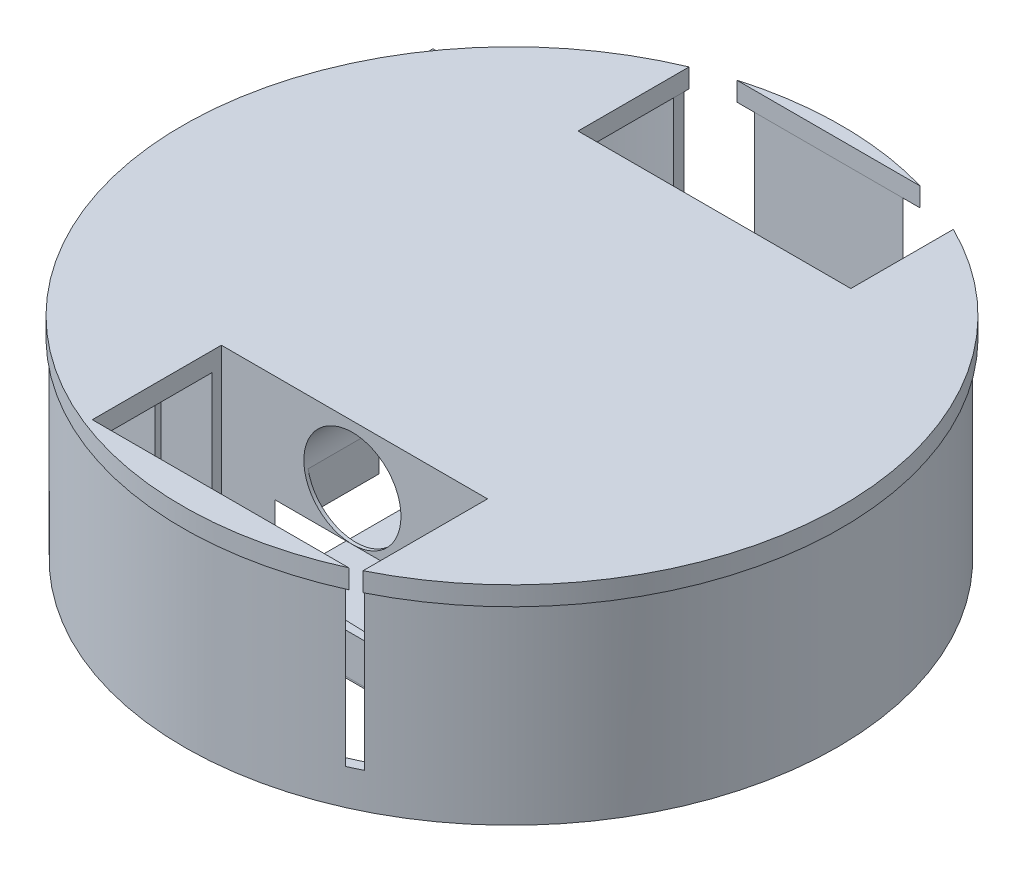
SolidWorks part; units mm, degrees
ref_plane "Front Plane" through (0, 0, 0) normal (0, 0, 1) x (1, 0, 0)
ref_plane "Top Plane" through (0, 0, 0) normal (0, 1, 0) x (1, 0, 0)
ref_plane "Right Plane" through (0, 0, 0) normal (1, 0, 0) x (0, 0, -1)
sketch "MotorHoldersSketch" plane through (0, 0, 0) normal (0, 0, 1) x (1, 0, 0)
  line L0 (0, 0) -> (170, 0) construction
  line L1 (0, 0) -> (0, 23.41) construction
  line L2 (170, 0) -> (170, 23.41) construction
  circle A1 centre (170, 0) radius 23.41
ref_axis "MotorCenterAxis1" through (0, 0, 0) along (0, 0, 1)
ref_axis "MotorCenterAxis2" through (170, 0, 0) along (0, 0, 1)
extrude "MotorHolders" add sketch "MotorHoldersSketch" along normal blind 80 and the other way blind 80
sketch "Sketch3" plane through (0, 0, 0) normal (0, 0, 1) x (1, 0, 0)
  line L1 (1.9406, 21.133) -> (168.3435, 21.133)
  line L2 (1.9406, 21.133) -> (1.9406, 18.3155)
  line L3 (1.9406, 18.3155) -> (168.3435, 18.3155)
  line L4 (168.3435, 21.133) -> (168.3435, 18.3155)
sketch "Sketch4" plane through (0, 0, 0) normal (0, 1, 0) x (1, 0, 0)
  line L1 (221.2811, -76.3794) -> (-41.4939, -76.3794)
  line L2 (221.2811, -76.3794) -> (221.2811, 76.7331)
  line L3 (221.2811, 76.7331) -> (-41.4939, 76.7331)
  line L4 (-41.4939, -76.3794) -> (-41.4939, 76.7331)
extrude "Cut-Extrude1" cut sketch "Sketch4" against normal blind 26
ref_axis "Axis3" through (170, 0, 0) along (0, -1, 0)
sketch3d "ReferencePlanePosition"
  line L0 (170, 0, 0) -> (170, -34.8293, 0)
  line L1 (170, 0, 0) -> (170, -38.994, 0) construction
ref_plane "ReferencePlane" through (170, -34.8293, 0) normal (0, -1, 0) x (-1, 0, 0)
sketch "Sketch6" plane through (170, -34.8293, 0) normal (0, -1, 0) x (-1, 0, 0)
  line L1 (118.9411, 77.3242) -> (78.3714, 77.3242)
  line L2 (118.9411, 77.3242) -> (118.9411, 63.9034)
  line L3 (118.9411, 63.9034) -> (78.3714, 63.9034)
  line L4 (78.3714, 77.3242) -> (78.3714, 63.9034)
  line L5 (102.8829, -41.5305) -> (78.545, -41.5305)
  line L6 (102.8829, -41.5305) -> (102.8829, -79.7918)
  line L7 (102.8829, -79.7918) -> (78.545, -79.7918)
  line L8 (78.545, -41.5305) -> (78.545, -79.7918)
  line L9 (75.6651, 77.8627) -> (19.9904, 77.8627)
  line L10 (75.6651, 77.8627) -> (75.6651, 40.7512)
  line L11 (75.6651, 40.7512) -> (19.9904, 40.7512)
  line L12 (19.9904, 77.8627) -> (19.9904, 40.7512)
  line L13 (76.5596, -44.1716) -> (20.0852, -44.1716)
  line L14 (76.5596, -44.1716) -> (76.5596, -79.4437)
  line L15 (76.5596, -79.4437) -> (20.0852, -79.4437)
  line L16 (20.0852, -44.1716) -> (20.0852, -79.4437)
  line L21 (41.3552, 69.1777) -> (28.5109, 69.1777)
  line L22 (41.3552, 69.1777) -> (41.3552, 50.8413)
  line L23 (41.3552, 50.8413) -> (28.5109, 50.8413)
  line L24 (28.5109, 69.1777) -> (28.5109, 50.8413)
  line L25 (43.3068, -72.8101) -> (32.1723, -72.8101)
  line L26 (43.3068, -72.8101) -> (43.3068, -54.7747)
  line L27 (43.3068, -54.7747) -> (32.1723, -54.7747)
  line L28 (32.1723, -72.8101) -> (32.1723, -54.7747)
  line L29 (101.8834, -71.9977) -> (88.494, -71.9977)
  line L30 (101.8834, -71.9977) -> (101.8834, -61.6501)
  line L31 (101.8834, -61.6501) -> (88.494, -61.6501)
  line L32 (88.494, -71.9977) -> (88.494, -61.6501)
  line L37 (66.2772, 51.3198) -> (53.8697, 51.3198)
  line L38 (66.2772, 51.3198) -> (66.2772, 67.7632)
  line L39 (66.2772, 67.7632) -> (53.8697, 67.7632)
  line L40 (53.8697, 51.3198) -> (53.8697, 67.7632)
  line L45 (68.2481, -69.8638) -> (51.7107, -69.8638)
  line L46 (68.2481, -69.8638) -> (68.2481, -55.4273)
  line L47 (68.2481, -55.4273) -> (51.7107, -55.4273)
  line L48 (51.7107, -69.8638) -> (51.7107, -55.4273)
  line L49 (-20.7001, -79.4437) -> (-48.8506, -79.4437)
  line L50 (-20.7001, -79.4437) -> (-20.7001, -54.5097)
  line L51 (-20.7001, -54.5097) -> (-48.8506, -54.5097)
  line L52 (-48.8506, -79.4437) -> (-48.8506, -54.5097)
  line L53 (-18.3873, 77.8627) -> (-49.0581, 77.8627)
  line L54 (-18.3873, 77.8627) -> (-18.3873, 51.5325)
  line L55 (-18.3873, 51.5325) -> (-49.0581, 51.5325)
  line L56 (-49.0581, 77.8627) -> (-49.0581, 51.5325)
  line L57 (-41.8141, -72.8101) -> (-31.6362, -72.8101)
  line L58 (-41.8141, -72.8101) -> (-41.8141, -62.9794)
  line L59 (-41.8141, -62.9794) -> (-31.6362, -62.9794)
  line L60 (-31.6362, -72.8101) -> (-31.6362, -62.9794)
  line L61 (-31.6362, 69.1777) -> (-41.5347, 69.1777)
  line L62 (-31.6362, 69.1777) -> (-31.6362, 58.5421)
  line L63 (-31.6362, 58.5421) -> (-41.5347, 58.5421)
  line L64 (-41.5347, 69.1777) -> (-41.5347, 58.5421)
extrude "PowerBankHolders" add sketch "Sketch6" along normal blind 30 and the other way blind 59 separate body
sketch3d "3DSketch3"
  line L0 (170, 0, 0) -> (170, -64.5, 0) construction
ref_plane "Plane2" through (170, -64.5, 0) normal (0, -1, 0) x (-1, 0, 0)
sketch "Sketch7" plane through (170, -64.5, 0) normal (0, -1, 0) x (-1, 0, 0)
  line L1 (-9.5047, -80.801) -> (181.32, -80.801)
  line L2 (-9.5047, -80.801) -> (-9.5047, 73.8662)
  line L3 (-9.5047, 73.8662) -> (181.32, 73.8662)
  line L4 (181.32, -80.801) -> (181.32, 73.8662)
  line L5 (151.8712, -54.3972) -> (26.5361, -54.3972)
  line L6 (151.8712, -54.3972) -> (151.8712, 46.2413)
  line L7 (151.8712, 46.2413) -> (26.5361, 46.2413)
  line L8 (26.5361, -54.3972) -> (26.5361, 46.2413)
ref_point "Point1"
sketch "MotorHolderExtrudeSketch" plane through (0, 0, 0) normal (0, 0, 1) x (1, 0, 0)
  circle A0 centre (170, 0) radius 20.415
  circle A4 centre (170, 0) radius 23.41 construction
ref_point "TopOfMotors"
ref_plane "TangentToTopOfMotors" through (0, -20.415, 0) normal (0, 1, 0) x (1, 0, 0)
ref_plane "BottomOfPowerBankRegion" through (0, -20.425, 0) normal (0, 1, 0) x (1, 0, 0)
ref_point "CenterAtBottomOfPowerBank"
ref_plane "TopOfPowerBankPlane" through (0, -54.425, 0) normal (0, 1, 0) x (1, 0, 0)
sketch "Sketch13" plane through (0, -54.425, 0) normal (0, 1, 0) x (1, 0, 0)
  line L1 (-19.4498, 72.5454) -> (166.1636, 72.5454)
  line L2 (-19.4498, 72.5454) -> (-19.4498, -78.2051)
  line L3 (-19.4498, -78.2051) -> (166.1636, -78.2051)
  line L4 (166.1636, 72.5454) -> (166.1636, -78.2051)
  line L5 (19.3173, -49.583) -> (137.9607, -49.583)
  line L6 (19.3173, -49.583) -> (19.3173, -21.0549)
  line L7 (19.3173, -21.0549) -> (137.9607, -21.0549)
  line L8 (137.9607, -49.583) -> (137.9607, -21.0549)
  line L9 (19.3173, 56.6778) -> (137.9607, 56.6778)
  line L10 (19.3173, 56.6778) -> (19.3173, 36.3234)
  line L11 (19.3173, 36.3234) -> (137.9607, 36.3234)
  line L12 (137.9607, 56.6778) -> (137.9607, 36.3234)
  line L13 (19.3173, 18.3186) -> (137.9607, 18.3186)
  line L14 (19.3173, 18.3186) -> (19.3173, -7.3615)
  line L15 (19.3173, -7.3615) -> (137.9607, -7.3615)
  line L16 (137.9607, 18.3186) -> (137.9607, -7.3615)
sketch "Sketch15" plane through (150.0096, 0, 0) normal (1, 0, 0) x (0, 0, -1)
  line L1 (72.5313, -25.7765) -> (45.7099, -25.7765)
  line L2 (72.5313, -25.7765) -> (72.5313, -24.2242)
  line L3 (72.5313, -24.2242) -> (45.7099, -24.2242)
  line L4 (45.7099, -25.7765) -> (45.7099, -24.2242)
ref_plane "Plane6" through (0, 0, 0) normal (0, 0, 1) x (1, 0, 0)
sketch "MotorGeometry1" plane through (0, 0, 0) normal (0, 0, 1) x (1, 0, 0)
  line L0 (170, 0) -> (170, -13.42)
  line L1 (170, 0) -> (170, -34.8293) construction
  line L2 (170, -13.42) -> (162.25, -13.42) construction
  line L3 (170, -13.42) -> (177.75, -13.42) construction
  line L4 (170, -13.42) -> (170, 7) construction
  line L5 (170, 0) -> (185.5, 0) construction
  line L6 (170, 0) -> (154.5, 0) construction
  line L7 (170, 0) -> (170, 13.42) construction
  line L8 (170, 0) -> (170, 23.41) construction
  line L9 (170, 13.42) -> (177.75, 13.42) construction
  line L10 (170, 13.42) -> (162.25, 13.42)
ref_axis "BoltAxisA" through (185.5, 0, 0) along (0, 0, 1)
ref_axis "BoltAxisB" through (177.75, -13.42, 0) along (0, 0, 1)
ref_axis "BoltAxisC" through (162.25, -13.42, 0) along (0, 0, 1)
ref_axis "BoltAxisD" through (154.5, 0, 0) along (0, 0, 1)
ref_axis "BoltAxisE" through (162.25, 13.42, 0) along (0, 0, 1)
ref_axis "BoltAxisF" through (177.75, 13.42, 0) along (0, 0, 1)
ref_point "Point6"
ref_point "Point7"
ref_point "Point8"
ref_point "Point9"
ref_point "Point10"
ref_point "Point11"
ref_point "Point12"
ref_point "Point13"
ref_point "Point14"
ref_point "Point15"
ref_point "Point16"
ref_point "Point17"
ref_plane "BottomPlane" through (0, 19.575, 0) normal (0, 1, 0) x (1, 0, 0)
ref_point "Point35"
ref_axis "OutputShaftReference2" through (170, 7, 0) along (0, 0, 1)
sketch "Sketch21" plane through (0, 19.575, 0) normal (0, 1, 0) x (1, 0, 0)
  line L0 (219.6842, -79.5488) -> (-50.341, -79.5488) construction
  line L1 (-50.341, -79.5488) -> (-50.341, 79.7899) construction
  line L2 (-50.341, 79.7899) -> (219.6842, 79.7899) construction
  line L3 (219.6842, 79.7899) -> (219.6842, -79.5488) construction
  circle A1 centre (165.3029, -3.6826) radius 138.5
extrude "BottomPlate" add sketch "Sketch21" along normal blind 5 and the other way blind 3
ref_plane "HoleReferencePlane1" through (0, 0, 80) normal (0, 0, 1) x (1, 0, 0)
ref_point "OutputShaftPosition3"
sketch "Sketch23" plane through (0, 0, 80) normal (0, 0, 1) x (1, 0, 0)
  line L5 (121.3218, 21.8402) -> (204.258, 21.8402)
  line L6 (121.3218, 21.8402) -> (121.3218, -65.2231)
  line L7 (121.3218, -65.2231) -> (204.258, -65.2231)
  line L8 (204.258, 21.8402) -> (204.258, -65.2231)
extrude "MotorMountingSupport1" add sketch "Sketch23" against normal blind 6
ref_plane "HoleReferencePlane2" through (0, 0, -80) normal (0, 0, -1) x (-1, 0, 0)
ref_point "OutputShaftPosition4"
sketch "Sketch24" plane through (0, 0, -80) normal (0, 0, -1) x (-1, 0, 0)
  line L1 (-202.1905, -67.1257) -> (-139.5471, -67.1257)
  line L2 (-202.1905, -67.1257) -> (-202.1905, 19.2374)
  line L3 (-202.1905, 19.2374) -> (-139.5471, 19.2374)
  line L4 (-139.5471, -67.1257) -> (-139.5471, 19.2374)
extrude "MotorMountingSuppor2" add sketch "Sketch24" against normal blind 6
sketch "Sketch17" plane through (0, 0, 80) normal (0, 0, 1) x (1, 0, 0)
  circle A0 centre (185.5, 0) radius 2.1
  circle A1 centre (177.75, -13.42) radius 2.1
  circle A2 centre (162.25, -13.42) radius 2.1
  circle A3 centre (154.5, 0) radius 2.1
  circle A4 centre (162.25, 13.42) radius 2.1
  circle A5 centre (177.75, 13.42) radius 2.1
  circle A6 centre (170, 7) radius 7.5
extrude "MotorHoles1" cut sketch "Sketch17" against normal blind 31.5
sketch "Sketch19" plane through (0, 0, -80) normal (0, 0, -1) x (-1, 0, 0)
  circle A0 centre (-185.5, 0) radius 2.1
  circle A1 centre (-177.75, -13.42) radius 2.1
  circle A2 centre (-162.25, -13.42) radius 2.1
  circle A3 centre (-154.5, 0) radius 2.1
  circle A4 centre (-162.25, 13.42) radius 2.1
  circle A5 centre (-177.75, 13.42) radius 2.1
  circle A6 centre (-170, 7) radius 7.5
extrude "Cut-Extrude4" cut sketch "Sketch19" against normal blind 30
ref_plane "Front" through (219.0581, 0, 0) normal (1, 0, 0) x (0, 0, -1)
sketch "Sketch29" plane through (219.0581, 0, 0) normal (1, 0, 0) x (0, 0, -1)
  line L1 (76.6955, -63.9254) -> (-77.9397, -63.9254)
  line L2 (76.6955, -63.9254) -> (76.6955, 20.2062)
  line L3 (76.6955, 20.2062) -> (-77.9397, 20.2062)
  line L4 (-77.9397, -63.9254) -> (-77.9397, 20.2062)
  line L5 (-13.4507, -48.1531) -> (12.5493, -48.1531)
  line L6 (-13.4507, -48.1531) -> (-13.4507, -28.9404)
  line L7 (-13.4507, -28.9404) -> (12.5493, -28.9404)
  line L8 (12.5493, -48.1531) -> (12.5493, -28.9404)
extrude "Boss-Extrude8" add sketch "Sketch29" against normal blind 3
ref_plane "Plane12" through (0, -64.8293, 0) normal (0, -1, 0) x (-1, 0, 0)
sketch "Sketch28" plane through (0, -64.8293, 0) normal (0, -1, 0) x (-1, 0, 0)
  line L1 (-189.3897, -79.549) -> (-123.0026, -79.549)
  line L2 (-189.3897, -79.549) -> (-189.3897, 78.1499)
  line L3 (-189.3897, 78.1499) -> (-123.0026, 78.1499)
  line L4 (-123.0026, -79.549) -> (-123.0026, 78.1499)
extrude "CellPhonePlate" add sketch "Sketch28" along normal blind 1.5 and the other way blind 2.5
sketch "Sketch11" plane through (0, -20.425, 0) normal (0, 1, 0) x (1, 0, 0)
  line L0 (-125.013, 7.5612) -> (295.013, -7.5612) construction
  line L5 (55.0389, -72.8934) -> (55.0389, 75.0508)
  line L6 (295.013, 65.2564) -> (295.013, -80.3788)
  line L7 (295.013, -80.3788) -> (55.0389, -72.8934)
  line L8 (295.013, 65.2564) -> (55.0389, 75.0508)
  point P0 (85, 0)
extrude "PowerBankCut" cut sketch "Sketch11" against normal up to surface (44.4043 mm away) up to face at (206.7252, -64.8293, 67.8947)
extrude "MotorHolderCut" cut sketch "MotorHolderExtrudeSketch" against normal blind 77 and the other way blind 77
sketch "Sketch31" plane through (219.0581, 0, 0) normal (1, 0, 0) x (0, 0, -1)
  line L0 (49.4417, -6.1927) -> (49.4417, -19.3739)
  line L1 (49.4417, -19.3739) -> (42.9342, -21.6341)
  line L2 (42.9342, -21.6341) -> (40.0618, -21.6341)
  line L3 (40.0618, -21.6341) -> (37.7863, -19.3586)
  line L4 (37.7863, -19.3586) -> (37.7863, -15.3813)
  line L5 (37.7863, -15.3813) -> (40.0618, -13.1059)
  line L6 (40.0618, -13.1059) -> (37.7863, -6.5545)
  line L7 (37.7863, -6.5545) -> (41.498, -6.5545)
  line L8 (41.498, -6.5545) -> (43.4004, -12.0319)
  line L9 (43.4004, -12.0319) -> (46.389, -12.0319)
  line L10 (46.389, -12.0319) -> (46.389, -6.5545)
  line L11 (46.389, -6.5545) -> (49.4417, -6.1927)
  line L12 (33.0193, -21.6341) -> (33.0193, -9.8302)
  line L13 (33.0193, -9.8302) -> (30.5402, -7.3511)
  line L14 (30.5402, -7.3511) -> (25.7203, -7.3511)
  line L15 (25.7203, -7.3511) -> (23.2412, -9.8302)
  line L16 (23.2412, -9.8302) -> (23.2412, -21.6341)
  line L17 (23.2412, -21.6341) -> (25.7203, -21.6341)
  line L18 (25.7203, -21.6341) -> (25.7203, -10.7454)
  line L19 (25.7203, -10.7454) -> (30.5402, -10.7454)
  line L20 (30.5402, -10.7454) -> (30.5402, -21.6341)
  line L21 (30.5402, -21.6341) -> (33.0193, -21.6341)
  line L22 (19.7226, -8.5907) -> (19.7226, -21.6341)
  line L23 (19.7226, -21.6341) -> (13.8207, -15.7322)
  line L24 (13.8207, -15.7322) -> (13.8207, -21.6341)
  line L25 (13.8207, -21.6341) -> (10.7708, -21.6341)
  line L26 (10.7708, -21.6341) -> (10.7708, -8.5907)
  line L27 (10.7708, -8.5907) -> (16.7716, -14.5915)
  line L28 (16.7716, -14.5915) -> (16.7716, -8.5907)
  line L29 (16.7716, -8.5907) -> (19.7226, -8.5907)
  line L30 (7.3891, -8.5907) -> (7.3891, -21.6341)
  line L31 (7.3891, -21.6341) -> (3.7282, -21.6341)
  line L32 (3.7282, -21.6341) -> (1.3209, -17.37)
  line L33 (1.3209, -17.37) -> (-1.2519, -21.6341)
  line L34 (-1.2519, -21.6341) -> (-3.6554, -21.6341)
  line L35 (-3.6554, -21.6341) -> (-4.6916, -8.5907)
  line L36 (-4.6916, -8.5907) -> (-2.4537, -8.5907)
  line L37 (-2.4537, -8.5907) -> (0.0345, -15.7545)
  line L38 (0.0345, -15.7545) -> (1.3209, -13.6224)
  line L39 (1.3209, -13.6224) -> (4.8544, -15.7545)
  line L40 (4.8544, -15.7545) -> (4.8544, -8.5907)
  line L41 (4.8544, -8.5907) -> (7.3891, -8.5907)
  line L42 (-7.6823, -21.6341) -> (-10.9875, -15.7545)
  line L43 (-10.9875, -15.7545) -> (-10.9875, -8.5907)
  line L44 (-10.9875, -8.5907) -> (-15.3102, -8.5907)
  line L45 (-15.3102, -8.5907) -> (-15.3102, -15.7545)
  line L46 (-15.3102, -15.7545) -> (-19.2695, -21.6341)
  line L47 (-19.2695, -21.6341) -> (-15.3102, -21.6341)
  line L48 (-15.3102, -21.6341) -> (-13.1489, -18.4245)
  line L49 (-13.1489, -18.4245) -> (-10.9875, -22.2693)
  line L50 (-10.9875, -22.2693) -> (-7.6823, -21.6341)
  line L51 (46.389, -17.8857) -> (46.389, -14.5915)
  line L52 (46.389, -14.5915) -> (41.498, -14.5915)
  line L53 (41.498, -14.5915) -> (39.5067, -16.2541)
  line L54 (39.5067, -16.2541) -> (41.5656, -18.7201)
  line L55 (41.5656, -18.7201) -> (46.389, -17.8857)
  line L56 (-22.571, -8.5907) -> (-22.0989, -21.6341)
  line L57 (-22.0989, -21.6341) -> (-26.4915, -21.6341)
  line L58 (-26.4915, -21.6341) -> (-29.9116, -19.3586)
  line L59 (-29.9116, -19.3586) -> (-30.636, -15.7545)
  line L60 (-30.636, -15.7545) -> (-27.4135, -14.1052)
  line L61 (-27.4135, -14.1052) -> (-30.636, -8.5907)
  line L62 (-30.636, -8.5907) -> (-27.4135, -8.5907)
  line L63 (-27.4135, -8.5907) -> (-25.3987, -14.1052)
  line L64 (-25.3987, -14.1052) -> (-24.2952, -14.1052)
  line L65 (-24.2952, -14.1052) -> (-24.4948, -8.5907)
  line L66 (-24.4948, -8.5907) -> (-22.571, -8.5907)
  line L67 (-35.0099, -8.5907) -> (-38.6395, -8.5907)
  line L68 (-38.6395, -8.5907) -> (-41.5241, -13.6224)
  line L69 (-41.5241, -13.6224) -> (-41.5241, -18.4245)
  line L70 (-41.5241, -18.4245) -> (-38.6395, -21.3091)
  line L71 (-38.6395, -21.3091) -> (-35.0099, -21.3091)
  line L72 (-35.0099, -21.3091) -> (-32.4978, -18.797)
  line L73 (-32.4978, -18.797) -> (-32.4978, -14.1052)
  line L74 (-32.4978, -14.1052) -> (-35.0099, -8.5907)
  line L75 (-44.0593, -21.3091) -> (-44.0593, -8.5907)
  line L76 (-44.0593, -8.5907) -> (-49.4499, -8.5907)
  line L77 (-49.4499, -8.5907) -> (-52.2269, -11.3677)
  line L78 (-52.2269, -11.3677) -> (-52.2269, -14.1052)
  line L79 (-52.2269, -14.1052) -> (-50.5777, -15.7545)
  line L80 (-50.5777, -15.7545) -> (-52.2269, -17.4037)
  line L81 (-52.2269, -17.4037) -> (-52.2269, -19.3586)
  line L82 (-52.2269, -19.3586) -> (-49.4499, -21.3091)
  line L83 (-49.4499, -21.3091) -> (-44.0593, -21.3091)
  line L84 (-57.7977, -21.3091) -> (-55.6011, -19.1125)
  line L85 (-55.6011, -19.1125) -> (-55.6011, -10.7454)
  line L86 (-55.6011, -10.7454) -> (-59.2637, -8.5907)
  line L87 (-59.2637, -8.5907) -> (-61.7818, -8.5907)
  line L88 (-61.7818, -8.5907) -> (-63.9365, -10.7454)
  line L89 (-63.9365, -10.7454) -> (-63.9365, -19.1125)
  line L90 (-63.9365, -19.1125) -> (-61.7818, -21.2672)
  line L91 (-61.7818, -21.2672) -> (-57.7977, -21.3091)
  line L92 (-66.7918, -21.2672) -> (-74.8705, -21.2672)
  line L93 (-74.8705, -21.2672) -> (-74.8705, -19.1125)
  line L94 (-74.8705, -19.1125) -> (-72.2665, -19.1125)
  line L95 (-72.2665, -19.1125) -> (-72.2665, -8.5907)
  line L96 (-72.2665, -8.5907) -> (-69.9977, -8.5907)
  line L97 (-69.9977, -8.5907) -> (-69.9977, -19.1125)
  line L98 (-69.9977, -19.1125) -> (-66.7918, -19.1125)
  line L99 (-66.7918, -19.1125) -> (-66.7918, -21.2672)
  line L100 (-36.1114, -18.797) -> (-34.7181, -17.4037)
  line L101 (-34.7181, -17.4037) -> (-34.7181, -13.1059)
  line L102 (-34.7181, -13.1059) -> (-36.6627, -11.1613)
  line L103 (-36.6627, -11.1613) -> (-37.8659, -11.1613)
  line L104 (-37.8659, -11.1613) -> (-39.3107, -13.1059)
  line L105 (-39.3107, -13.1059) -> (-39.5155, -16.8544)
  line L106 (-39.5155, -16.8544) -> (-38.25, -18.7201)
  line L107 (-38.25, -18.7201) -> (-36.1114, -18.797)
  line L108 (-46.2436, -16.8544) -> (-48.9032, -16.8544)
  line L109 (-48.9032, -16.8544) -> (-49.4499, -18.4245)
  line L110 (-49.4499, -18.4245) -> (-48.0836, -19.3586)
  line L111 (-48.0836, -19.3586) -> (-46.2436, -19.3586)
  line L112 (-46.2436, -19.3586) -> (-46.2436, -16.8544)
  line L113 (-45.9206, -14.5915) -> (-45.9206, -11.1613)
  line L114 (-45.9206, -11.1613) -> (-49.2105, -10.7454)
  line L115 (-49.2105, -10.7454) -> (-50.1756, -12.8764)
  line L116 (-50.1756, -12.8764) -> (-48.5891, -14.5915)
  line L117 (-48.5891, -14.5915) -> (-45.9206, -14.5915)
  line L118 (-58.5672, -18.7201) -> (-57.7977, -17.4037)
  line L119 (-57.7977, -17.4037) -> (-57.7977, -11.7636)
  line L120 (-57.7977, -11.7636) -> (-59.6573, -10.7454)
  line L121 (-59.6573, -10.7454) -> (-60.8144, -10.7454)
  line L122 (-60.8144, -10.7454) -> (-62.101, -12.0319)
  line L123 (-62.101, -12.0319) -> (-61.7818, -17.4037)
  line L124 (-61.7818, -17.4037) -> (-60.8144, -18.7201)
  line L125 (-60.8144, -18.7201) -> (-58.5672, -18.7201)
  line L126 (-24.2952, -19.3586) -> (-24.2952, -16.2541)
  line L127 (-24.2952, -16.2541) -> (-26.4915, -16.2541)
  line L128 (-26.4915, -16.2541) -> (-27.4135, -17.1761)
  line L129 (-27.4135, -17.1761) -> (-27.4135, -18.4245)
  line L130 (-27.4135, -18.4245) -> (-26.3339, -19.5041)
  line L131 (-26.3339, -19.5041) -> (-24.2952, -19.3586)
extrude "Label" add sketch "Sketch31" along normal blind 1
sketch "Sketch37" plane through (0, -20.425, 0) normal (0, -1, 0) x (1, 0, 0)
  line L1 (144.416, -35.6729) -> (89.0759, -35.6729)
  line L2 (144.416, -35.6729) -> (144.416, -65.4438)
  line L3 (144.416, -65.4438) -> (89.0759, -65.4438)
  line L4 (89.0759, -35.6729) -> (89.0759, -65.4438)
sketch "Sketch42" plane through (0, 0, 80) normal (0, 0, 1) x (1, 0, 0)
  circle A0 centre (170, 7) radius 42
  circle A1 centre (170, 7) radius 54.5
extrude "Cut-Extrude10" cut sketch "Sketch42" against normal blind 5 and the other way blind 10
sketch "Sketch43" plane through (0, 0, -80) normal (0, 0, -1) x (-1, 0, 0)
  circle A0 centre (-170, 7) radius 42
  circle A1 centre (-170, 7) radius 54.5
extrude "Cut-Extrude11" cut sketch "Sketch43" against normal blind 5 and the other way blind 10
sketch "Sketch46" plane through (0, 16.575, 0) normal (0, -1, 0) x (1, 0, 0)
  line L1 (226.7934, 75.4637) -> (114.9281, 75.4637)
  line L2 (226.7934, 75.4637) -> (226.7934, 129.7054)
  line L3 (226.7934, 129.7054) -> (114.9281, 129.7054)
  line L4 (114.9281, 75.4637) -> (114.9281, 129.7054)
  line L5 (226.5792, -129.3408) -> (111.9219, -129.3408)
  line L6 (226.5792, -129.3408) -> (226.5792, -77.4474)
  line L7 (226.5792, -77.4474) -> (111.9219, -77.4474)
  line L8 (111.9219, -129.3408) -> (111.9219, -77.4474)
sketch "Sketch47" plane through (0, 16.575, 0) normal (0, -1, 0) x (1, 0, 0)
  circle A0 centre (165.467, 4.3217) radius 137.2638
  circle A1 centre (165.467, 4.3217) radius 133.0813
extrude "Boss-Extrude9" add sketch "Sketch47" along normal blind 80
extrude "Cut-Extrude13" cut sketch "Sketch46" against normal blind 45 and the other way blind 65
